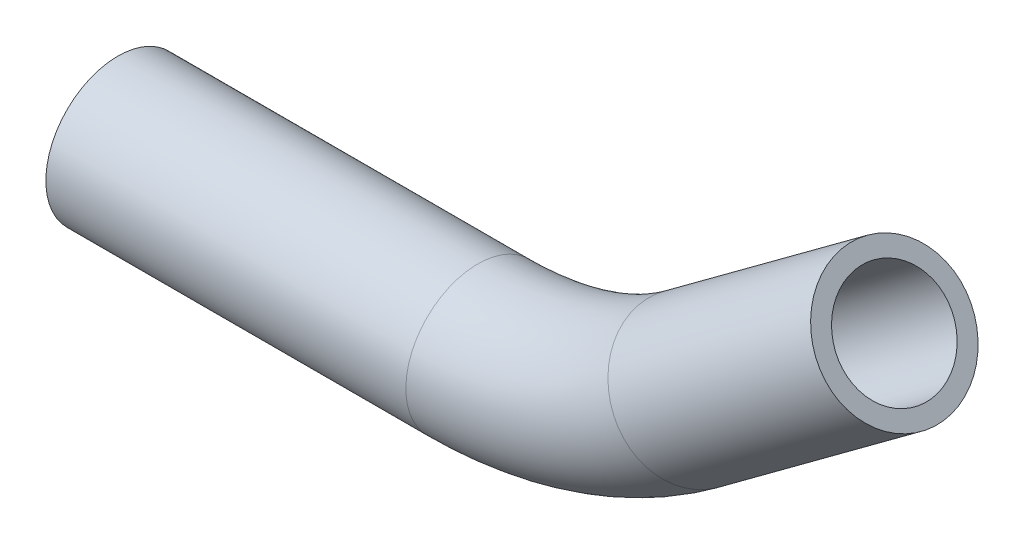
SolidWorks part; units mm, degrees
material "Сталь 3 ГОСТ 535-88"
ref_plane "Спереди" through (0, 0, 0) normal (0, 0, 1) x (1, 0, 0)
ref_plane "Сверху" through (0, 0, 0) normal (0, 1, 0) x (1, 0, 0)
ref_plane "Справа" through (0, 0, 0) normal (1, 0, 0) x (0, 0, -1)
sketch "Эскиз1" plane through (0, 0, 0) normal (0, 0, 1) x (1, 0, 0)
  line L0 (0, 0) -> (20, 0)
  line L1 (31.8823, 3.9124) -> (43.1436, 12.23)
  arc A0 (20, 0) -> (31.8823, 3.9124) centre (20, 20) ccw
  point P5 (0, 0)
  point P7 (56.9695, 28.5232)
  point P8 (86.4869, 94.2594)
  point P9 (87.1707, 71.3593)
  point P10 (49.3457, 14.9261)
  point P11 (73.554, 49.2342)
  point P12 (54.9407, 33.3402)
  point P13 (48.6415, 12.7546)
  point P14 (53.4288, 39.4344)
  point P15 (55.7632, 31.673)
  point P16 (110.9071, 54.8942)
  dimension "D1" = 20
  dimension "D2" = 20
  dimension "D3" = 14
sketch "Эскиз2" plane through (0, 0, 0) normal (1, 0, 0) x (0, 0, -1)
  circle A0 centre (0, 0) radius 4
  circle A1 centre (0, 0) radius 3
  dimension "D1" = 8
  dimension "D2" = 1
sweep "По траектории1" add profiles "Эскиз2" path "Эскиз1"
